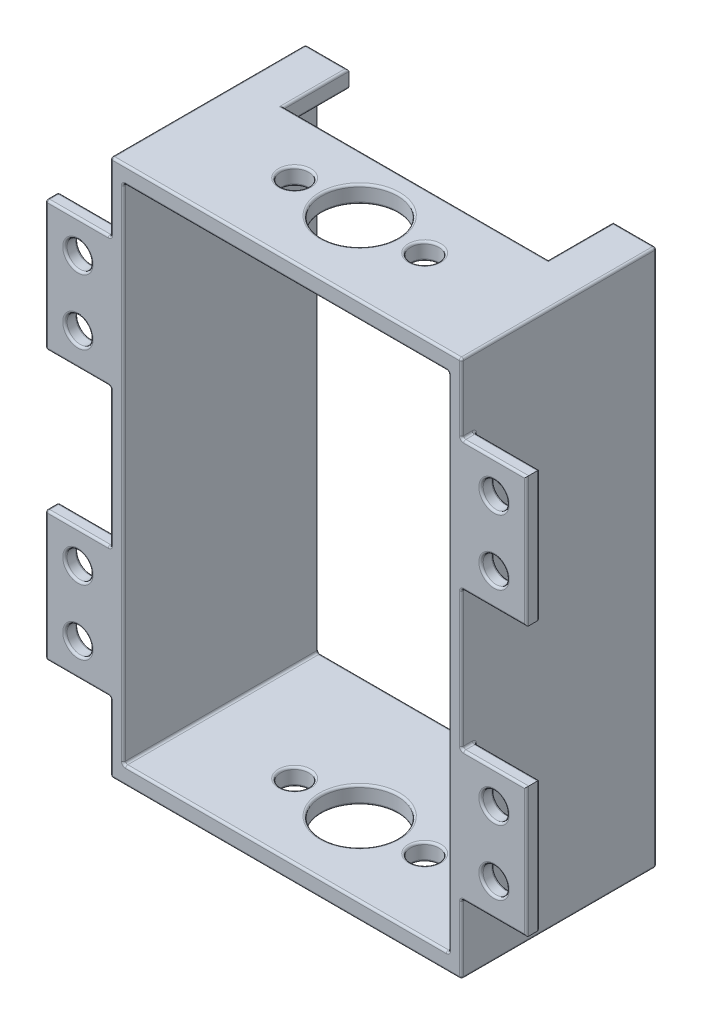
SolidWorks part; units mm, degrees
ref_plane "Front Plane" through (0, 0, 0) normal (0, 0, 1) x (1, 0, 0)
ref_plane "Top Plane" through (0, 0, 0) normal (0, 1, 0) x (1, 0, 0)
ref_plane "Right Plane" through (0, 0, 0) normal (1, 0, 0) x (0, 0, -1)
sketch "Sketch1" plane through (0, 0, 0) normal (0, 1, 0) x (1, 0, 0)
  line L0 (37.5, 45) -> (37.5, 0) construction
  line L1 (0, 0) -> (75, 0)
  line L2 (0, 0) -> (0, 45)
  line L3 (0, 45) -> (75, 45)
  line L4 (75, 0) -> (75, 45)
  line L5 (0, 17) -> (37.5, 17) construction
  line L6 (37.5, 17) -> (75, 17) construction
  circle A2 centre (37.5, 17) radius 8.75
  circle A5 centre (22.5, 17) radius 3.25
  circle A6 centre (52.5, 17) radius 3.25
  point P15 (0, 0)
  point P16 (68.593, 20)
  point P17 (0, 0)
  point P18 (8.724, 20)
  point P19 (0, 0)
  point P20 (0, 0)
  point P21 (0, 0)
  point P22 (0, 0)
  dimension "D2" = 6.5
  dimension "D3" = 17.5
  dimension "D1" = 45
  dimension "D4" = 75
  dimension "D5" = 15
  dimension "D6" = 17
extrude "Boss-Extrude1" add sketch "Sketch1" along normal blind 4
sketch "Sketch2" plane through (0, 0, 0) normal (-1, 0, 0) x (0, 0, 1)
  line L0 (-45, 4) -> (-45, 0) construction
  line L1 (0, 0) -> (-45, 0)
  line L2 (0, 0) -> (0, 120)
  line L3 (0, 120) -> (-45, 120)
  line L4 (-45, 0) -> (-45, 120)
  dimension "D1" = 120
extrude "Boss-Extrude2" add sketch "Sketch2" along normal blind 3
ref_plane "Plane1" through (37.5, 0, 0) normal (1, 0, 0) x (0, 0, -1)
mirror "Mirror1" about plane through (37.5, 0, 0) normal (1, 0, 0) of "Boss-Extrude2"
sketch "Sketch3" plane through (0, 120, 0) normal (0, 1, 0) x (1, 0, 0)
  line L1 (-3, 0) -> (78, 0)
  line L2 (-3, 0) -> (-3, 45)
  line L3 (-3, 45) -> (78, 45)
  line L4 (78, 0) -> (78, 45)
  circle A1 centre (37.5, 17) radius 8.75
  circle A2 centre (22.5, 17) radius 3.25
  circle A3 centre (22.5, 17) radius 3.25 construction
  circle A4 centre (52.5, 17) radius 3.25
  circle A5 centre (52.5, 17) radius 3.25 construction
  circle A6 centre (37.5, 17) radius 8.75 construction
extrude "Boss-Extrude3" add sketch "Sketch3" along normal blind 4
sketch "Sketch5" plane through (0, 0, 0) normal (0, 0, 1) x (1, 0, 0)
  line L0 (78, 62) -> (-3, 62) construction
  line L1 (78, 0) -> (78, 124) construction
  line L2 (-3, 0) -> (-3, 124) construction
  line L3 (78, 124) -> (-3, 62) construction
  line L4 (-3, 78) -> (-18, 78)
  line L5 (-3, 78) -> (-3, 108)
  line L6 (-3, 108) -> (-18, 108)
  line L7 (-18, 78) -> (-18, 108)
  line L8 (-3, 108) -> (-18, 93) construction
  line L9 (-18, 93) -> (-3, 93) construction
  line L10 (-3, 16) -> (-18, 16)
  line L11 (-18, 46) -> (-18, 16)
  line L12 (-3, 46) -> (-18, 46)
  line L13 (-3, 46) -> (-3, 16)
  circle A0 centre (-10.5, 100.5) radius 3
  circle A1 centre (-10.5, 85.5) radius 3
  circle A2 centre (-10.5, 38.5) radius 3
  circle A3 centre (-10.5, 23.5) radius 3
  point P11 (37.5, 93)
  point P13 (-3, 93)
  dimension "D3" = 6
  dimension "D1" = 15
  dimension "D2" = 30
extrude "Boss-Extrude5" add sketch "Sketch5" against normal blind 3
mirror "Mirror2" about plane through (37.5, 0, 0) normal (1, 0, 0) of "Boss-Extrude5"
sketch "Sketch6" plane through (0, 124, 0) normal (0, 1, 0) x (1, 0, 0)
  line L0 (37.5, 45) -> (37.5, 0) construction
  line L1 (78, 45) -> (-3, 45) construction
  line L2 (-3, 0) -> (78, 0) construction
  line L4 (7, 45) -> (68, 45)
  line L5 (7, 45) -> (7, 30)
  line L6 (7, 30) -> (68, 30)
  line L7 (68, 45) -> (68, 30)
  line L11 (-3, 45) -> (-3, 0) construction
  point P10 (37.5, 45)
  dimension "D1" = 10
  dimension "D2" = 15
extrude "Cut-Extrude1" cut sketch "Sketch6" against normal up to next
fillet "Fillet1" radius 0.5 104 edges at (71.5, 120, -45) (3.5, 120, -45) (37.5, 4, -45) (-3, 62, -45) (-3, 108, -1.5) (-3, 78, -1.5) (-3, 46, -1.5) (-3, 16, -1.5) (75, 62, -45) (75, 120, -22.5) (75, 4, -22.5) (0, 120, -22.5) (0, 62, -45) (0, 4, -22.5) (52.5, 124, -13.75) (22.5, 124, -13.75) (37.5, 124, -8.25) (-3, 124, -22.5) (2, 124, -45) (7, 124, -37.5) (37.5, 124, -30) (68, 124, -37.5) (73, 124, -45) (88.5, 23.5, 0) (82.5, 38.5, 0) (88.5, 85.5, 0) (82.5, 100.5, 0) (-7.5, 38.5, 0) (-13.5, 23.5, 0) (-7.5, 100.5, 0) (-13.5, 85.5, 0) (-3, 8, 0) (-10.5, 16, 0) (-10.5, 46, 0) (-3, 62, 0) (-10.5, 78, 0) (-10.5, 108, 0) (-3, 116, 0) (37.5, 124, 0) (85.5, 108, 0) (93, 93, 0) (85.5, 78, 0) (85.5, 46, 0) (93, 31, 0) (85.5, 16, 0) (37.5, 4, 0) (75, 62, 0) (37.5, 120, 0) (0, 62, 0) (88.5, 23.5, -3) (85.5, 16, -3) (93, 31, -3) (85.5, 46, -3) (82.5, 38.5, -3) (88.5, 85.5, -3) (82.5, 100.5, -3) (85.5, 78, -3) (93, 93, -3) (85.5, 108, -3) (78, 78, -1.5) (78, 93, -3) (78, 108, -1.5) (78, 116, 0) (78, 124, -22.5) (78, 62, -45) (78, 8, 0) (78, 16, -1.5) (78, 31, -3) (78, 46, -1.5) (78, 62, 0) (37.5, 0, -8.25) (22.5, 0, -13.75) (78, 0, -22.5) (37.5, 0, -45) (-3, 0, -22.5) (37.5, 0, 0) (52.5, 0, -20.25) (-10.5, 108, -3) (-10.5, 78, -3) (-3, 93, -3) (-7.5, 100.5, -3) (-13.5, 85.5, -3) (-10.5, 46, -3) (-10.5, 16, -3) (-3, 31, -3) (-7.5, 38.5, -3) (-13.5, 23.5, -3) (-18, 78, -1.5) (-18, 93, -3) (-18, 108, -1.5) (-18, 93, 0) (-18, 16, -1.5) (-18, 31, -3) (-18, 46, -1.5) (-18, 31, 0) (52.5, 120, -13.75) (37.5, 120, -8.25) (22.5, 120, -13.75) (37.5, 120, -30) (7, 120, -37.5) (68, 120, -37.5) (37.5, 4, -8.25) (52.5, 4, -20.25) (22.5, 4, -13.75)
equation "\"length\"=120"
equation "\"D1@Sketch2\"=\"length\""
equation "\"D3@LPattern1\"=\"length\""
